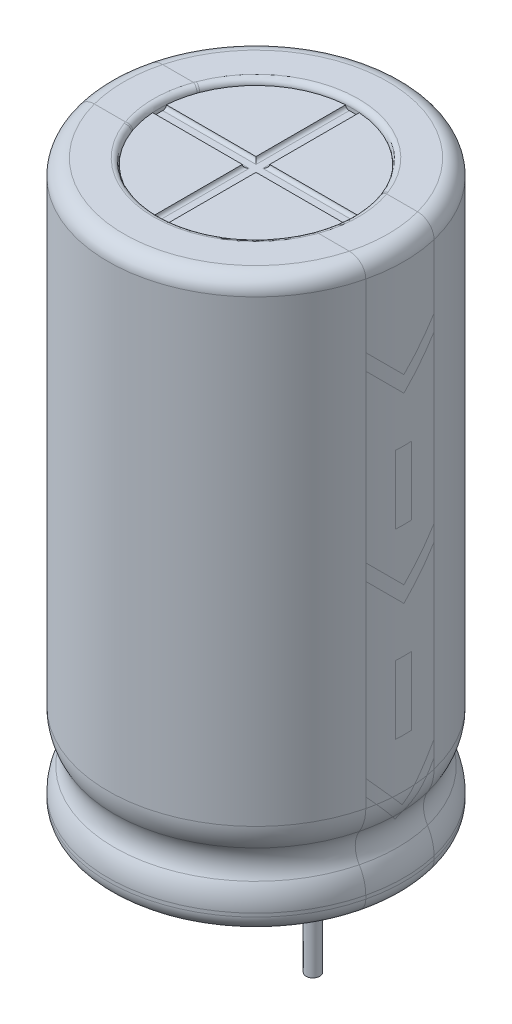
SolidWorks part; units mm, degrees
ref_plane "Front Plane" through (0, 0, 0) normal (0, 0, 1) x (1, 0, 0)
ref_plane "Top Plane" through (0, 0, 0) normal (0, 1, 0) x (1, 0, 0)
ref_plane "Right Plane" through (0, 0, 0) normal (1, 0, 0) x (0, 0, -1)
sketch "Эскиз1" plane through (0, 0, 0) normal (0, 0, 1) x (1, 0, 0)
  line L0 (0, 47.0384) -> (0, -50.5015) construction
  line L1 (0, 0) -> (-6.5, 0)
  line L2 (-6.5, 0) -> (-6.5, 1.5395)
  line L3 (-6.5, 25) -> (0, 25)
  line L4 (0, 25) -> (0, 0)
  line L5 (-6.5, 3.4605) -> (-6.5, 25)
  arc A0 (-6.5, 1.5395) -> (-6.5, 3.4605) centre (-7.3, 2.5) ccw
  dimension "D3" = 2.5
  dimension "D1" = 6.5
  dimension "D2" = 25
  dimension "D4" = 0.8
  dimension "D5" = 2.5
revolve "Повернуть2" add sketch "Эскиз1" angle 360 about L0
sketch "Эскиз2" plane through (0, 25, 0) normal (0, 1, 0) x (1, 0, 0)
  circle A0 centre (0, 0) radius 4.25
  dimension "D1" = 8.5
extrude "Вырез-Вытянуть1" cut sketch "Эскиз2" against normal blind 0.25
sketch "Эскиз3" plane through (0, 24.75, 0) normal (0, 1, 0) x (1, 0, 0)
  line L0 (0, 5.3403) -> (0, -5.4999) construction
  line L1 (-5.5664, 0) -> (5.593, 0) construction
  line L2 (-0.3, 4.2394) -> (-0.3, 0.3)
  line L3 (-0.3, 0.3) -> (-4.2394, 0.3)
  line L4 (0.3, 0.3) -> (4.2394, 0.3)
  line L5 (0.3, 4.2394) -> (0.3, 0.3)
  line L6 (0.3, -0.3) -> (4.2394, -0.3)
  line L7 (0.3, -4.2394) -> (0.3, -0.3)
  line L8 (-0.3, -4.2394) -> (-0.3, -0.3)
  line L9 (-0.3, -0.3) -> (-4.2394, -0.3)
  circle A0 centre (0, 0) radius 4.25 construction
  arc A1 (-4.2394, 0.3) -> (-4.2394, -0.3) centre (0, 0) ccw
  arc A2 (0.3, 4.2394) -> (-0.3, 4.2394) centre (0, 0) ccw
  arc A3 (4.2394, -0.3) -> (4.2394, 0.3) centre (0, 0) ccw
  arc A4 (-0.3, -4.2394) -> (0.3, -4.2394) centre (0, 0) ccw
  dimension "D1" = 0.3
  dimension "D2" = 0.3
extrude "Вырез-Вытянуть2" cut sketch "Эскиз3" against normal blind 0.15
fillet "Скругление1" radius 0.7 2 edges at (0, 0, 6.5) (0, 25, 6.5)
fillet "Скругление2" radius 2 2 edges at (0, 1.5395, 6.5) (0, 3.4605, 6.5)
sketch "Эскиз4" plane through (0, 0, 0) normal (0, -1, 0) x (1, 0, 0)
  line L0 (0, 5.3536) -> (0, -5.5664) construction
  line L1 (-5.8457, 0) -> (5.2871, 0) construction
  circle A1 centre (0, 0) radius 4.25
  dimension "D1" = 8.5
extrude "Вырез-Вытянуть3" cut sketch "Эскиз4" against normal blind 0.25
sketch "Эскиз5" plane through (0, 0.25, 0) normal (0, -1, 0) x (1, 0, 0)
  line L0 (0, 5.3137) -> (0, -5.593) construction
  line L1 (-5.4467, 0) -> (5.3536, 0) construction
  circle A0 centre (-2.5, 0) radius 0.3
  circle A1 centre (2.5, 0) radius 0.3
  dimension "D1" = 0.6
  dimension "D2" = 2.5
extrude "Бобышка-Вытянуть1" add sketch "Эскиз5" along normal blind 5
fillet "Скругление3" radius 0.15 8 edges at (0.3, 24.6, -2.2697) (-2.2697, 24.6, 0.3) (2.2697, 24.6, 0.3) (0.3, 24.6, 2.2697) (-0.3, 24.6, 2.2697) (2.2697, 24.6, -0.3) (-0.3, 24.6, -2.2697) (-2.2697, 24.6, -0.3)
ref_plane "Плоскость1" through (5.5, 0, 0) normal (1, 0, 0) x (0, 0, -1)
sketch "Эскиз6" plane through (5.5, 0, 0) normal (1, 0, 0) x (0, 0, -1)
  line L0 (0, 22.3182) -> (0, -7.8953) construction
  line L1 (4.25, 25) -> (-4.25, 25) construction
  line L2 (-1.5, 30) -> (1.5, 30)
  line L3 (-1.5, 30) -> (-1.5, 0)
  line L4 (-1.5, 0) -> (1.5, 0)
  line L5 (1.5, 30) -> (1.5, 0)
  line L6 (-1.5, 30) -> (1.5, 0) construction
  line L7 (-1.5, 0) -> (1.5, 30) construction
  line L8 (-1.5, 21.5) -> (0, 20)
  line L9 (0, 20) -> (1.5, 21.5)
  line L10 (1.5, 21.5) -> (1.5, 20.7929)
  line L11 (1.5, 20.7929) -> (0, 19.2929)
  line L12 (0, 19.2929) -> (-1.5, 20.7929)
  line L13 (-1.5, 20.7929) -> (-1.5, 21.5)
  line L14 (-1.5, 11.2929) -> (-1.5, 12)
  line L15 (-0.35, 17.2929) -> (0.35, 17.2929)
  line L16 (-0.35, 17.2929) -> (-0.35, 14.2929)
  line L17 (-0.35, 14.2929) -> (0.35, 14.2929)
  line L18 (0.35, 17.2929) -> (0.35, 14.2929)
  line L19 (-0.35, 17.2929) -> (0.35, 14.2929) construction
  line L20 (-0.35, 14.2929) -> (0.35, 17.2929) construction
  line L23 (1.5, 12) -> (1.5, 11.2929)
  line L30 (-0.35, 7.7929) -> (-0.35, 4.7929) [skipped]
  line L31 (0.35, 7.7929) -> (0.35, 4.7929) [skipped]
  line L32 (-0.35, 4.7929) -> (0.35, 4.7929) [skipped]
  line L33 (-0.35, 7.7929) -> (0.35, 7.7929) [skipped]
  line L34 (0, 9.7929) -> (-1.5, 11.2929) [skipped]
  line L35 (-1.5, 12) -> (0, 10.5) [skipped]
  line L36 (0, 10.5) -> (1.5, 12) [skipped]
  line L37 (1.5, 11.2929) -> (0, 9.7929) [skipped]
  line L38 (-1.5, 12.7929) -> (-1.5, 13.5)
  line L39 (-1.5, 13.5) -> (0, 12)
  line L40 (0, 12) -> (1.5, 13.5)
  line L41 (1.5, 13.5) -> (1.5, 12.7929)
  line L42 (1.5, 12.7929) -> (0, 11.2929)
  line L43 (0, 11.2929) -> (-1.5, 12.7929)
  line L44 (-0.35, 9.2929) -> (-0.35, 6.2929)
  line L45 (-0.35, 9.2929) -> (0.35, 9.2929)
  line L46 (0.35, 9.2929) -> (0.35, 6.2929)
  line L47 (-0.35, 6.2929) -> (0.35, 6.2929)
  line L48 (-1.5, 5.2929) -> (0, 3.5929)
  line L49 (0, 3.5929) -> (1.5, 5.2929)
  line L50 (1.5, 5.2929) -> (1.5, 4.5929)
  line L51 (1.5, 4.5929) -> (0, 2.8929)
  line L52 (0, 2.8929) -> (-1.5, 4.5929)
  line L53 (-1.5, 4.5929) -> (-1.5, 5.2929)
  line L54 (6.5, 4.15) -> (-6.5, 4.15) construction
  point P3 (0, 15)
  point P12 (0, 15.7929)
  dimension "D1" = 30
  dimension "D2" = 3
  dimension "D3" = 5
  dimension "D4" = 0.5
  dimension "D5" = 5
  dimension "D6" = 2.1213
  dimension "D7" = 2
  dimension "D8" = 3
  dimension "D9" = 0.7
  dimension "D12" = 0.7
  dimension "D13" = 0.7
  dimension "D14" = 0.7
  dimension "D15" = 1.7
  dimension "D16" = 2.1429
  dimension "D17" = 2.7
  dimension "D10" = 2
  dimension "D11" = 2
split line "Разделяющая линия1"
fillet "Скругление4" radius 0.25 4 edges at (0, 25, 4.25) (4.25, 25, 0) (0, 25, -4.25) (-4.25, 25, 0)
fillet "Скругление5" radius 0.25 4 edges at (0, 0, 4.25) (-4.25, 0, 0) (0, 0, -4.25) (4.25, 0, 0)
